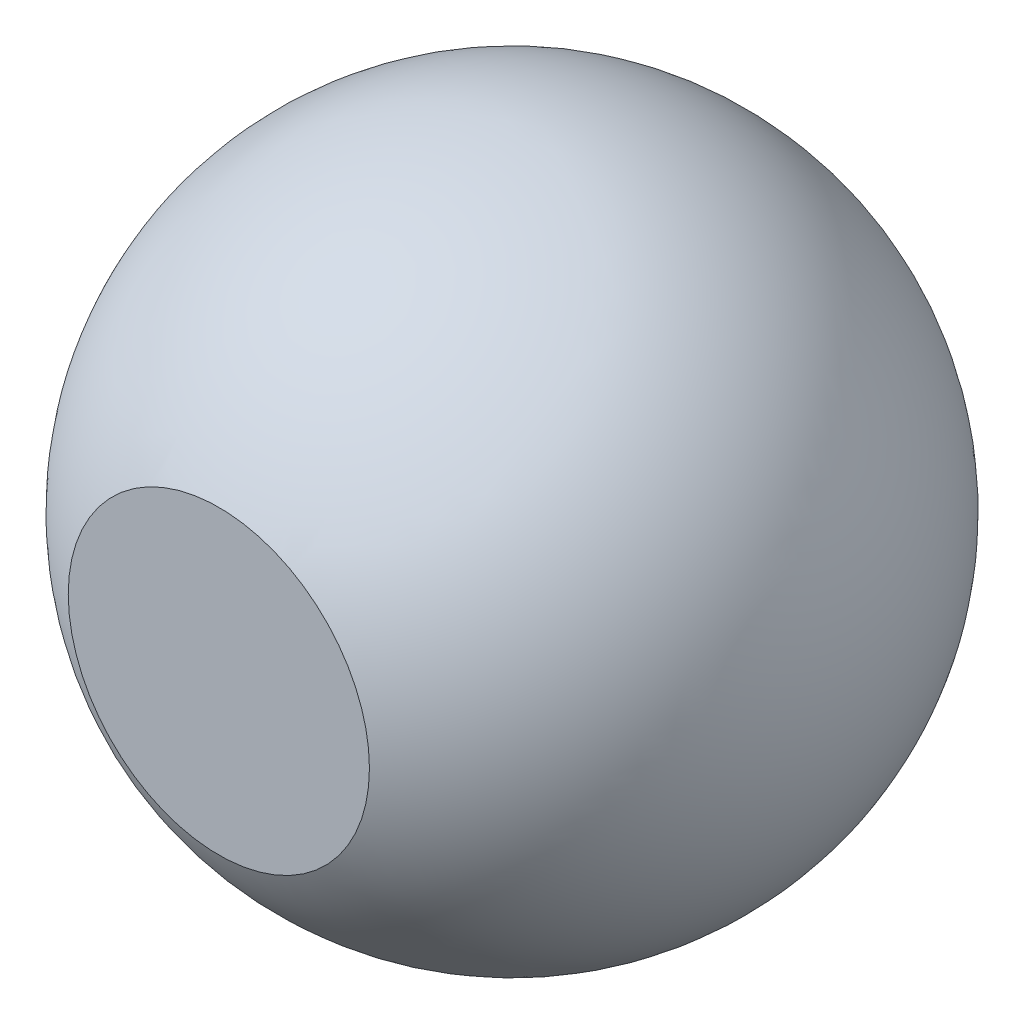
SolidWorks part; units mm, degrees
ref_plane "Ön Düzlem" through (0, 0, 0) normal (0, 0, 1) x (1, 0, 0)
ref_plane "Üst Düzlem" through (0, 0, 0) normal (0, 1, 0) x (1, 0, 0)
ref_plane "Sağ Düzlem" through (0, 0, 0) normal (1, 0, 0) x (0, 0, -1)
sketch "Çizim6" plane through (0, 0, 0) normal (0, 0, 1) x (1, 0, 0)
  line L0 (-4.5, 0) -> (4.5, 0)
  arc A0 (4.5, 0) -> (-4.5, 0) centre (0, 0) ccw
revolve "Döndür1" add sketch "Çizim6" angle 360 about L0
ref_plane "Düzlem4" through (0, 0, 4) normal (0, 0, 1) x (1, 0, 0)
sketch "Çizim8" plane through (0, 0, 0) normal (1, 0, 0) x (0, 0, -1)
  line L0 (-4.0028, 2.2566) -> (-4.0028, -2.9282)
  line L1 (-4.0028, -2.9282) -> (-6.0983, -2.9282)
  line L2 (-6.0983, -2.9282) -> (-6.0983, 2.2566)
  line L3 (-6.0983, 2.2566) -> (-4.0028, 2.2566)
  line L4 (2.2163, -4.0163) -> (-2.6193, -4.0163)
  line L5 (-2.6193, -4.0163) -> (-2.6193, -5.1043)
  line L6 (-2.6193, -5.1043) -> (2.2163, -5.1043)
  line L7 (2.2163, -5.1043) -> (2.2163, -4.0163)
extrude "Kes-Ekstrüzyon1" cut sketch "Çizim8" against normal blind 10 and the other way blind 10
